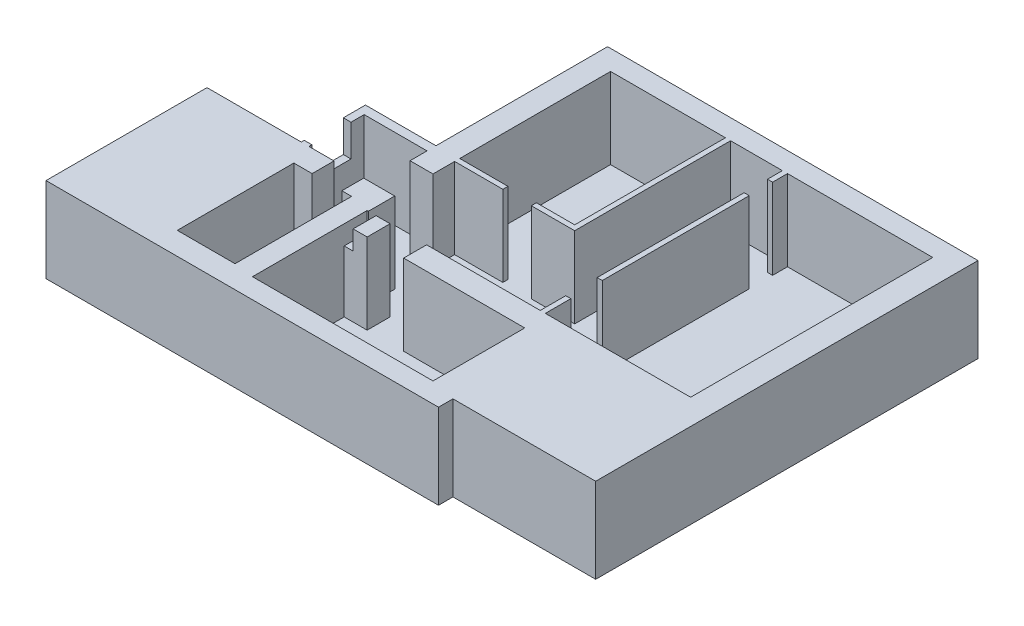
SolidWorks part; units mm, degrees
ref_plane "Спереди" through (0, 0, 0) normal (0, 0, 1) x (1, 0, 0)
ref_plane "Сверху" through (0, 0, 0) normal (0, 1, 0) x (1, 0, 0)
ref_plane "Справа" through (0, 0, 0) normal (1, 0, 0) x (0, 0, -1)
sketch "Эскиз1" plane through (0, 0, 0) normal (0, 1, 0) x (1, 0, 0)
  line L1 (-12600, 0) -> (-12600, 3790)
  line L2 (-12600, 3790) -> (-10380, 3790)
  line L3 (-10380, 3790) -> (-10380, 3860)
  line L4 (-10380, 5300) -> (-8720, 5300)
  line L5 (-8720, 5300) -> (-8720, 9340)
  line L6 (-8720, 9340) -> (0, 9340)
  line L7 (0, 9340) -> (0, 2250)
  line L8 (0, 2250) -> (-2025, 2250) construction
  line L9 (-2025, 2250) -> (-2025, 0) construction
  line L10 (-2025, 2250) -> (-3395, 2250) construction
  line L11 (-3395, 2250) -> (-3395, 0) construction
  line L12 (-9310, 5300) -> (-9310, 6480) construction
  line L13 (-9310, 6480) -> (-8720, 6480) construction
  line L14 (-2285, 2250) -> (-2285, 1725) construction
  line L15 (-2285, 1725) -> (-2025, 1725) construction
  line L16 (-2025, 350) -> (-2375, 350) construction
  line L17 (-2375, 350) -> (-2375, 0) construction
  line L18 (-9610, 3790) -> (-9610, 3275)
  line L19 (-9610, 3275) -> (-10040, 3275)
  line L20 (-10040, 3275) -> (-10040, 530)
  line L21 (-10040, 530) -> (-8680, 530)
  line L22 (-8680, 530) -> (-8680, 3275)
  line L23 (-8680, 3275) -> (-8910, 3275)
  line L24 (-8910, 3275) -> (-8910, 3790)
  line L25 (-9610, 3790) -> (-10200, 3790)
  line L26 (-10380, 3860) -> (-10200, 3860)
  line L27 (-10200, 3860) -> (-10200, 3790)
  line L28 (-10380, 4780) -> (-10200, 4780)
  line L29 (-10200, 4780) -> (-10200, 5090)
  line L30 (-10200, 5090) -> (-8720, 5090)
  line L31 (-8720, 5090) -> (-8720, 4690)
  line L32 (-10380, 4780) -> (-10380, 5300)
  line L33 (-8720, 4690) -> (-8180, 4690)
  line L34 (-8180, 4690) -> (-8180, 5200)
  line L35 (-8910, 3790) -> (-8180, 3790)
  line L36 (-6810, 2630) -> (-3960, 2630)
  line L37 (-3960, 2630) -> (-3960, 470)
  line L38 (-8180, 3790) -> (-8180, 3170)
  line L39 (-8180, 3170) -> (-7670, 3170)
  line L40 (-7670, 3170) -> (-7670, 2630)
  line L41 (-6810, 2630) -> (-6810, 3170)
  line L42 (-6810, 3170) -> (-4135, 3170)
  line L43 (-7670, 2630) -> (-8210, 2630)
  line L44 (-8210, 2630) -> (-8210, 470)
  line L45 (-8210, 470) -> (-3960, 470)
  line L46 (-4135, 7970) -> (-4135, 4510)
  line L47 (-8180, 5200) -> (-7045, 5200)
  line L49 (-7045, 5200) -> (-7045, 5320)
  line L50 (-7045, 5320) -> (-8180, 5320)
  line L51 (-8180, 5320) -> (-8180, 8870)
  line L52 (-8180, 8870) -> (-5475, 8870)
  line L53 (-5475, 8870) -> (-5475, 5320)
  line L54 (-5475, 5320) -> (-6375, 5320)
  line L55 (-6375, 5320) -> (-6375, 5200)
  line L56 (-6375, 5200) -> (-5355, 5200)
  line L57 (-4015, 4510) -> (-4015, 7970)
  line L58 (-595, 3170) -> (-595, 8870)
  line L59 (-4135, 3170) -> (-4135, 3770)
  line L60 (-4135, 3770) -> (-4015, 3770)
  line L61 (-4015, 3770) -> (-4015, 3170)
  line L62 (-4015, 3170) -> (-595, 3170)
  line L63 (-4135, 4510) -> (-4015, 4510)
  line L64 (-4015, 7970) -> (-4135, 7970)
  line L65 (-595, 8870) -> (-4015, 8870)
  line L66 (-4015, 8870) -> (-4015, 8520)
  line L67 (-4015, 8520) -> (-4135, 8520)
  line L68 (-4135, 8520) -> (-4135, 8870)
  line L69 (-4135, 8870) -> (-5355, 8870)
  line L70 (-5355, 8870) -> (-5355, 5200)
  line L71 (-3360, 0) -> (-3360, 340)
  line L72 (0, 2250) -> (0, 340)
  line L74 (-3360, 340) -> (0, 340)
  line L75 (-3360, 0) -> (-12600, 0)
  line L76 (-3395, 0) -> (0, 0) construction
  line L77 (0, 0) -> (0, 340) construction
  dimension "D1" = 8720
  dimension "D3" = 2250
  dimension "D4" = 2025
  dimension "D5" = 9205
  dimension "D6" = 3880
  dimension "D7" = 3790
  dimension "D8" = 2220
  dimension "D9" = 1510
  dimension "D10" = 120
  dimension "D11" = 525
  dimension "D12" = 260
  dimension "D13" = 350
  dimension "D14" = 590
  dimension "D15" = 1180
  dimension "D16" = 700
  dimension "D17" = 3260
  dimension "D18" = 1360
  dimension "D19" = 770
  dimension "D20" = 515
  dimension "D21" = 1300
  dimension "D22" = 180
  dimension "D23" = 310
  dimension "D24" = 920
  dimension "D25" = 430
  dimension "D26" = 1220
  dimension "D27" = 900
  dimension "D28" = 4250
  dimension "D29" = 540
  dimension "D30" = 620
  dimension "D31" = 540
  dimension "D32" = 510
  dimension "D33" = 860
  dimension "D34" = 540
  dimension "D35" = 2160
  dimension "D36" = 4045
  dimension "D37" = 2030
  dimension "D38" = 900
  dimension "D39" = 3420
  dimension "D40" = 3540
  dimension "D41" = 670
  dimension "D42" = 3360
  dimension "D43" = 600
  dimension "D44" = 1340
  dimension "D45" = 5700
  dimension "D46" = 350
  dimension "D47" = 900
  dimension "D48" = 340
  dimension "D51" = 2705
  dimension "D53" = 920
extrude "Бобышка-Вытянуть1" add sketch "Эскиз1" along normal blind 1900
sketch "Эскиз2" plane through (0, 0, 0) normal (0, -1, 0) x (1, 0, 0)
  line L0 (0, -9340) -> (-8720, -9340) construction
  line L1 (0, -9340) -> (-8720, -9340)
  line L2 (0, -340) -> (0, -9340) construction
  line L3 (0, -340) -> (0, -9340)
  line L4 (-12600, 0) -> (-3360, 0) construction
  line L8 (-12600, 0) -> (-3360, 0)
  line L10 (-8720, -9340) -> (-8720, -5300) construction
  line L11 (-8720, -5300) -> (-10380, -5300) construction
  line L12 (-10380, -5300) -> (-10380, -4780) construction
  line L13 (-10380, -3790) -> (-12600, -3790) construction
  line L14 (-12600, -3790) -> (-12600, 0) construction
  line L15 (-8720, -9340) -> (-8720, -5300)
  line L16 (-8720, -5300) -> (-10380, -5300)
  line L17 (-10380, -5300) -> (-10380, -3790)
  line L18 (-10380, -3790) -> (-12600, -3790)
  line L19 (-12600, -3790) -> (-12600, 0)
  line L20 (-3360, -340) -> (0, -340) construction
  line L21 (-3360, -340) -> (0, -340)
  line L22 (-3360, 0) -> (-3360, -340) construction
  line L23 (-3360, 0) -> (-3360, -340)
extrude "Бобышка-Вытянуть2" add sketch "Эскиз2" along normal blind 100
ref_plane "Плоскость1" through (0, 1100, 0) normal (0, 1, 0) x (1, 0, 0)
ref_axis "Ось1" through (-3360, 1100, 0) along (-1, 0, 0)
ref_axis "Ось2" through (0, 1100, -9340) along (0, 0, 1)
ref_point "Точка1"
sketch "Эскиз3" plane through (-10380, 0, 0) normal (-1, 0, 0) x (0, 0, 1)
  line L0 (-3860, 1900) -> (-3860, 0) construction
  line L1 (-4780, 0) -> (-3860, 0)
  line L2 (-4780, 0) -> (-4780, 1150)
  line L3 (-4780, 1150) -> (-3860, 1150)
  line L4 (-3860, 0) -> (-3860, 1150)
  line L5 (-3790, -100) -> (-5300, -100) construction
  dimension "D1" = 1250
extrude "Бобышка-Вытянуть3" add sketch "Эскиз3" against normal up to surface (180 mm away) up to face at (-10200, 950, -4935)
sketch "Эскиз4" plane through (0, 0, -2630) normal (0, 0, 1) x (1, 0, 0)
  line L0 (-8210, 1900) -> (-8210, 0) construction
  line L1 (-8210, 1447.5298) -> (-7999.6831, 1447.5298)
  line L2 (-8210, 1447.5298) -> (-8210, 1900)
  line L3 (-8210, 1900) -> (-7999.6831, 1900)
  line L4 (-7999.6831, 1447.5298) -> (-7999.6831, 1900)
  line L5 (-8210, 1900) -> (-7670, 1900) construction
extrude "Вырез-Вытянуть1" cut sketch "Эскиз4" against normal up to surface (540 mm away) up to face at (-7925, 950, -3170)
